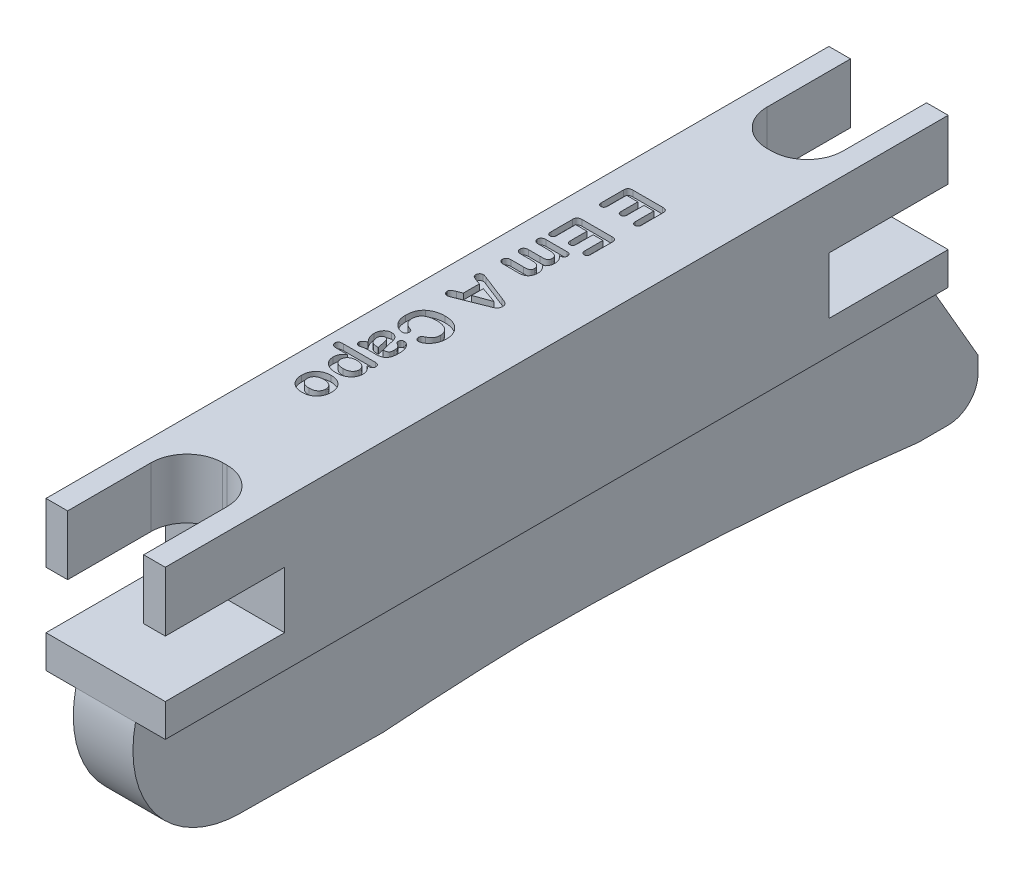
SolidWorks part; units mm, degrees
ref_plane "Front Plane" through (0, 0, 0) normal (0, 0, 1) x (1, 0, 0)
ref_plane "Top Plane" through (0, 0, 0) normal (0, 1, 0) x (1, 0, 0)
ref_plane "Right Plane" through (0, 0, 0) normal (1, 0, 0) x (0, 0, -1)
sketch "Sketch2" plane through (0, 0, 0) normal (0, 1, 0) x (1, 0, 0)
  line L1 (0, 0) -> (10.16, 0)
  line L2 (0, 0) -> (0, 66.675)
  line L3 (0, 66.675) -> (10.16, 66.675)
  line L4 (10.16, 0) -> (10.16, 66.675)
  dimension "D1" = 66.675
  dimension "D2" = 10.16
extrude "Boss-Extrude1" add sketch "Sketch2" along normal blind 12.7
sketch "Sketch3" plane through (0, 0, 0) normal (0, -1, 0) x (1, 0, 0)
  line L0 (10.16, -66.675) -> (0, -66.675) construction
  line L1 (2.54, 0) -> (7.62, 0) construction
  line L2 (2.54, 0) -> (2.54, -66.675)
  line L3 (2.54, -66.675) -> (7.62, -66.675) construction
  line L4 (7.62, 0) -> (7.62, -66.675)
  line L5 (0, -66.675) -> (0, 0) construction
  line L6 (0, 0) -> (10.16, 0) construction
  line L7 (2.54, 0) -> (2.54, 5.08)
  line L8 (2.54, 5.08) -> (7.62, 5.08)
  line L9 (7.62, 5.08) -> (7.62, 0)
  line L10 (2.54, -66.675) -> (2.54, -71.755)
  line L11 (2.54, -71.755) -> (7.62, -71.755)
  line L12 (7.62, -71.755) -> (7.62, -66.675)
  dimension "D1" = 5.08
  dimension "D2" = 2.54
  dimension "D3" = 5.08
extrude "Boss-Extrude2" add sketch "Sketch3" along normal blind 12.7
sketch "Sketch4" plane through (0, 0, 0) normal (0, 0, 1) x (1, 0, 0)
  line L0 (0, 12.7) -> (10.16, 12.7) construction
  line L1 (0, 7.62) -> (1.8415, 7.62)
  line L2 (0, 7.62) -> (0, 2.794)
  line L3 (0, 2.794) -> (10.16, 2.794)
  line L4 (10.16, 7.62) -> (10.16, 2.794)
  line L5 (1.8415, 12.7) -> (8.3185, 12.7)
  line L6 (1.8415, 12.7) -> (1.8415, 7.62)
  line L8 (8.3185, 12.7) -> (8.3185, 7.62)
  line L9 (8.3185, 7.62) -> (10.16, 7.62)
  line L10 (10.16, 12.7) -> (10.16, 0) construction
  line L11 (0, 12.7) -> (0, 0) construction
  point P10 (5.08, 12.7)
  dimension "D2" = 6.477
  dimension "D3" = 4.826
  dimension "D4" = 5.08
extrude "Cut-Extrude1" cut sketch "Sketch4" against normal blind 10.16
ref_plane "Plane1" through (0, 0, -33.3375) normal (0, 0, 1) x (1, 0, 0)
fillet "Fillet2" radius 3.048 2 edges at (8.3185, 10.16, -10.16) (1.8415, 10.16, -10.16)
mirror "Mirror1" about plane through (0, 0, -33.3375) normal (0, 0, 1) of "Fillet2", "Cut-Extrude1"
sketch "Sketch5" plane through (2.54, 0, 0) normal (-1, 0, 0) x (0, 0, 1)
  line L0 (-33.3375, -10.668) -> (-33.3375, -12.7) construction
  line L1 (5.08, -12.7) -> (-71.755, -12.7) construction
  line L2 (-66.675, -12.7) -> (0, -12.7)
  line L3 (5.08, -12.7) -> (-71.755, -12.7) construction
  arc A0 (-66.675, -12.7) -> (0, -12.7) centre (-33.3375, -285.1557) cw
  dimension "D1" = 2.032
extrude "Cut-Extrude4" cut sketch "Sketch5" against normal through all
chamfer "Chamfer1" distance 5.08 angle 60 2 edges at (5.08, 0, 5.08) (5.08, 0, -71.755) first distance on face at (5.08, 0, 2.54) first distance on face at (5.08, 0, -69.215)
sketch "Sketch9" plane through (2.54, 0, 0) normal (-1, 0, 0) x (0, 0, 1)
  line L0 (5.08, -12.7) -> (5.08, -13.716)
  line L1 (5.08, -13.716) -> (0, -13.716)
  line L16 (5.08, -12.7) -> (5.08, -8.7988)
  line L17 (5.08, -8.7988) -> (0, 0)
  line L18 (0, 0) -> (-66.675, 0)
  line L19 (-66.675, 0) -> (-71.755, -8.7988)
  line L20 (-71.755, -8.7988) -> (-71.755, -12.7)
  line L21 (-71.755, -12.7) -> (-66.675, -12.7)
  line L22 (0, -12.7) -> (5.08, -12.7)
  line L23 (5.08, -12.7) -> (5.08, -8.7988)
  line L24 (5.08, -8.7988) -> (0, 0)
  line L25 (0, 0) -> (-66.675, 0)
  line L26 (-66.675, 0) -> (-71.755, -8.7988)
  line L27 (-71.755, -8.7988) -> (-71.755, -12.7)
  line L28 (-71.755, -12.7) -> (-66.675, -12.7)
  line L29 (0, -12.7) -> (5.08, -12.7)
  arc A0 (0, -12.7) -> (-66.675, -12.7) centre (-33.3375, -285.1557) ccw construction
  arc A1 (-33.3375, -10.668) -> (0, -13.716) centre (-40.6179, -274.1353) cw
  arc A2 (0, -12.7) -> (-66.675, -12.7) centre (-33.3375, -285.1557) ccw
  arc A3 (0, -12.7) -> (-66.675, -12.7) centre (-33.3375, -285.1557) ccw
  point P7 (0, 0)
  point P9 (0, 0)
  point P11 (-33.3375, -10.668)
  point P16 (-33.3375, -10.668)
  arc M16 (-66.675, -12.7) -> (0, -12.7) centre (-33.3375, -285.1557) cw
  line M17 (0, -12.7) -> (5.08, -12.7)
  dimension "D3" = 13.208
  dimension "D2" = 1.016
  dimension "D1" = 0
extrude "Boss-Extrude3" add sketch "Sketch9" against normal up to surface (5.08 mm away) contours A1 L1 L0 M16 M17 region at (2.54, -12.3116, -7.7036) up to face at (7.62, -8.2957, -33.3375)
sketch "Sketch6" plane through (0, 12.7, 0) normal (0, 1, 0) x (1, 0, 0)
  line L0 (1.8415, 7.112) -> (1.8415, 59.563) construction
  arc A0 (4.8895, 10.16) -> (1.8415, 7.112) centre (4.8895, 7.112) ccw construction
  text T0 "E Em A Capo" font "Arial Rounded MT Bold" height 3.5
extrude "Cut-Extrude5" cut sketch "Sketch6" against normal blind 0.508
sketch "Sketch8" plane through (2.54, 0, 0) normal (-1, 0, 0) x (0, 0, 1)
  line L0 (-33.3375, 0) -> (-33.3375, -10.668) construction
  line L2 (-8.89, -11.176) -> (-21.0748, -11.293)
  line L7 (5.08, -13.716) -> (5.08, -8.7988)
  line L8 (5.08, -8.7988) -> (0, 0)
  line L9 (0, 0) -> (-66.675, 0)
  line L10 (-66.675, 0) -> (-71.755, -8.7988)
  line L11 (-71.755, -8.7988) -> (-71.755, -12.7)
  line L12 (-71.755, -12.7) -> (-66.675, -12.7)
  line L13 (0, -13.716) -> (5.08, -13.716)
  line L14 (5.08, -13.716) -> (5.08, -8.7988)
  line L15 (5.08, -8.7988) -> (0, 0)
  line L16 (0, 0) -> (-66.675, 0)
  line L17 (-66.675, 0) -> (-71.755, -8.7988)
  line L18 (-71.755, -8.7988) -> (-71.755, -12.7)
  line L19 (-71.755, -12.7) -> (-66.675, -12.7)
  line L23 (0, -13.716) -> (5.08, -13.716)
  arc A1 (-33.3375, -10.668) -> (-66.675, -12.7) centre (-33.3375, -285.1557) ccw
  arc A2 (-33.3375, -10.668) -> (-66.675, -12.7) centre (-33.3375, -285.1557) ccw
  arc A3 (0, 0) -> (-8.89, -11.176) centre (-8.9783, -1.982) cw
  arc A5 (0, -13.716) -> (-33.3375, -10.668) centre (-40.6179, -274.1353) ccw
  arc A6 (0, -13.716) -> (-33.3375, -10.668) centre (-40.6179, -274.1353) ccw
  line M11 (5.08, -13.716) -> (5.08, -8.7988)
  line M12 (5.08, -8.7988) -> (0, 0)
  arc M17 (-66.675, -12.7) -> (-33.3375, -10.668) centre (-33.3375, -285.1557) cw
  dimension "D2" = 0.55
  dimension "D3" = 8.89
  dimension "D4" = 11.176
  dimension "D1" = 0
extrude "Cut-Extrude6" cut sketch "Sketch8" against normal through all contours M17 M11 M12 region at (2.54, -9.7817, -1.0713)
fillet "Fillet3" radius 2.54 1 edges at (5.08, -12.7, -71.755)
